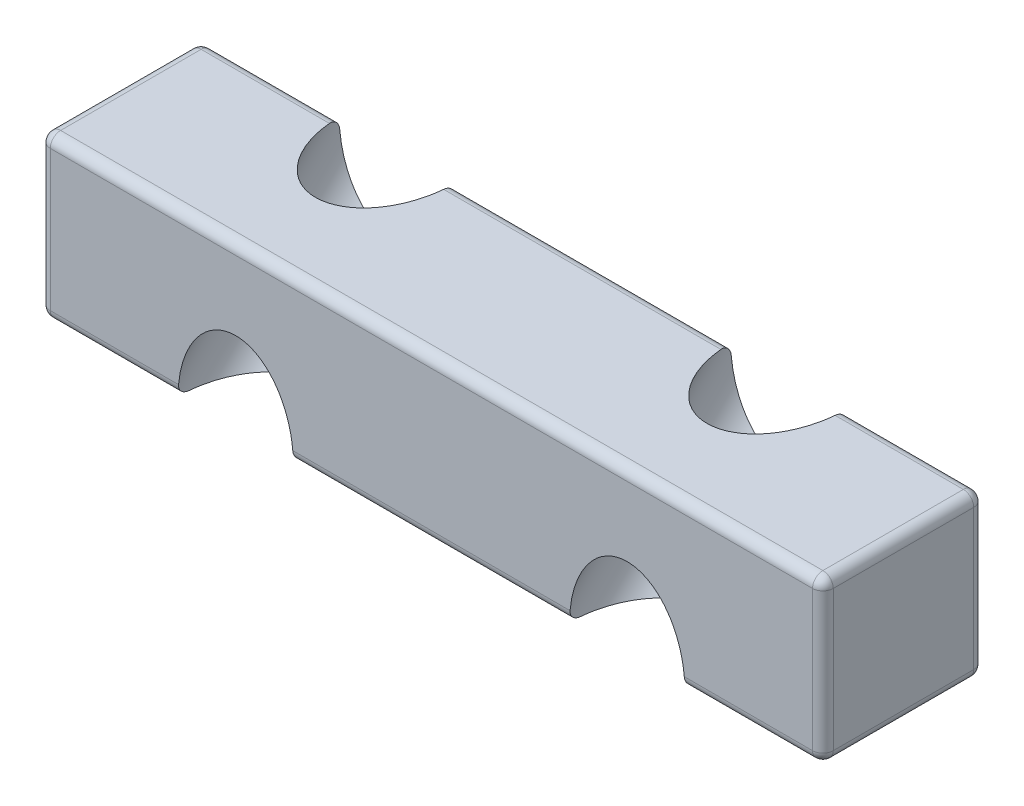
SolidWorks part; units mm, degrees
ref_plane "Front Plane" through (0, 0, 0) normal (0, 0, 1) x (1, 0, 0)
ref_plane "Top Plane" through (0, 0, 0) normal (0, 1, 0) x (1, 0, 0)
ref_plane "Right Plane" through (0, 0, 0) normal (1, 0, 0) x (0, 0, -1)
other "Configuration Table"
sketch "sketch1" plane through (0, 0, 0) normal (0, 1, 0) x (1, 0, 0)
  line L1 (0, 0) -> (34, 0)
  line L2 (0, 0) -> (0, -7)
  line L3 (0, -7) -> (34, -7)
  line L4 (34, 0) -> (34, -7)
  dimension "D1" = 7
  dimension "D2" = 34
extrude "Boss-Extrude1" add sketch "sketch1" along normal blind 7
ref_plane "Plane1" through (0, 0, 0) normal (0, 0.7071, -0.7071) x (-1, 0, 0)
sketch "Sketch6" plane through (0, 0, 0) normal (0, 0.7071, -0.7071) x (-1, 0, 0)
  line L0 (-34, 4.9497) -> (-25.5, 4.9497) construction
  line L1 (0, 0) -> (-34, 0)
  line L2 (0, 0) -> (0, 9.8995)
  line L3 (0, 9.8995) -> (-34, 9.8995)
  line L12 (-34, 0) -> (-34, 9.8995)
  line L13 (-25.5, 4.9497) -> (-8.5, 4.9497) construction
  circle A2 centre (-25.5, 4.9497) radius 2.5
  circle A3 centre (-8.5, 4.9497) radius 2.5
  dimension "D4" = 5
  dimension "D1" = 34
  dimension "D2" = 9.8995
  dimension "D3" = 8.5
  dimension "D6" = 17
  dimension "D5" = 2
extrude "Cut-Extrude2" cut sketch "Sketch6" against normal through all both and the other way through all flip side to cut
fillet "Fillet1" radius 0.45 16 edges at (31, 7, 0) (17, 7, 0) (3, 7, 0) (34, 0, 3.5) (34, 3.5, 0) (34, 7, 3.5) (34, 3.5, 7) (31, 0, 7) (3, 0, 7) (17, 0, 7) (17, 0, 0) (17, 7, 7) (0, 3.5, 0) (0, 3.5, 7) (0, 7, 3.5) (0, 0, 3.5)
equation "\"D2@sketch1\" = \"length\""
equation "\"holes\"= 2"
equation "\"cdist\"= 17mm'centre distance between holes"
equation "\"width\"= 7mm"
equation "\"length\"= \"cdist\" * \"holes\""
equation "\"D1@sketch1\" = \"width\""
equation "\"hdiam\"= 5.00mm'Hole diametre"
equation "\"D4@Sketch6\"=\"hdiam\""
equation "\"D1@Boss-Extrude1\"=\"width\""
equation "\"tolerance\"= 0.04mm"
equation "\"D1@Sketch6\"=\"length\""
equation "\"D2@Sketch6\"=sqr(\"width\"^2 + \"width\"^2)"
equation "\"D3@Sketch6\"=\"cdist\"/2"
equation "\"D5@Sketch6\"=\"holes\""
equation "\"D6@Sketch6\"=\"cdist\""
